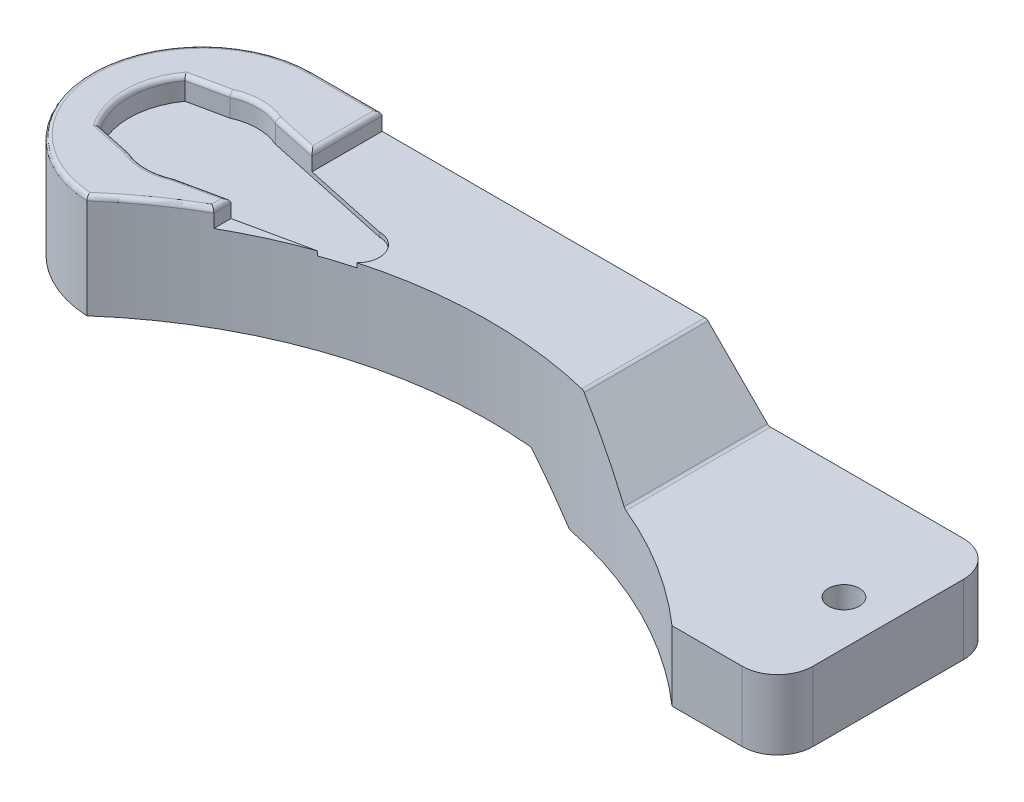
SolidWorks part; units mm, degrees
ref_plane "Front Plane" through (0, 0, 0) normal (0, 0, 1) x (1, 0, 0)
ref_plane "Top Plane" through (0, 0, 0) normal (0, 1, 0) x (1, 0, 0)
ref_plane "Right Plane" through (0, 0, 0) normal (1, 0, 0) x (0, 0, -1)
sketch "Sketch1" plane through (0, 0, 0) normal (0, 1, 0) x (1, 0, 0)
  line L1 (-45, 12.5) -> (45, 12.5)
  line L2 (-45, 12.5) -> (-45, -12.5)
  line L3 (-45, -12.5) -> (45, -12.5)
  line L4 (45, 12.5) -> (45, -12.5)
  dimension "D1" = 90
  dimension "D2" = 45
  dimension "D3" = 25
  dimension "D4" = 12.5
extrude "Boss-Extrude1" add sketch "Sketch1" along normal blind 16.87
sketch "Sketch3" plane through (0, 16.87, 0) normal (0, 1, 0) x (1, 0, 0)
  line L0 (-39.2721, 4.7988) -> (-35.061, 5.7012)
  line L5 (-45, 12.5) -> (-45, -12.5) construction
  line L6 (-45, -12.5) -> (45, -12.5) construction
  line L7 (-39.2721, -4.7988) -> (-35.061, -5.7012)
  line L9 (-29.939, 5.7012) -> (-15, 2.5)
  line L11 (-29.939, -5.7012) -> (-15, -2.5)
  arc A0 (-29.939, 5.7012) -> (-35.061, 5.7012) centre (-32.5, 0) ccw
  arc A1 (-15, -2.5) -> (-15, 2.5) centre (-15, 0) ccw
  arc A3 (-35.061, -5.7012) -> (-29.939, -5.7012) centre (-32.5, 0) ccw
  arc A4 (-39.2721, -4.7988) -> (-39.2721, 4.7988) centre (-32.5, 0) cw
  point P4 (0, 0)
  point P5 (-40.8, 0)
  point P10 (0, 0)
  point P12 (0, 0)
  dimension "D1" = 12.5
  dimension "D2" = 5
  dimension "D3" = 4.3067
  dimension "D14" = 8.3
  dimension "D4" = 4.3067
  dimension "D5" = 17.5
  dimension "D6" = 12.5
  dimension "D7" = 12.5
  dimension "D8" = 12.5
  dimension "D9" = 6.7721
  dimension "D10" = 6.7721
  dimension "D11" = 14.939
  dimension "D12" = 14.939
extrude "Cut-Extrude2" cut sketch "Sketch3" against normal blind 2.5
sketch "Esquisse2" plane through (0, 0, 12.5) normal (0, 0, 1) x (1, 0, 0)
  line L0 (10, 16.87) -> (19, 7.87)
  line L1 (45, 16.87) -> (10, 16.87)
  line L2 (45, 16.87) -> (45, 7.87)
  line L3 (45, 7.87) -> (10, 7.87)
  line L4 (10, 16.87) -> (10, 7.87)
  line L5 (-45, 0) -> (10, 0)
  line L8 (10, 0) -> (10, 7.87)
  line L9 (10, 0) -> (4.88, 5.12)
  line L10 (4.88, 5.12) -> (-45, 5.12)
  line L11 (-45, 5.12) -> (-45, 0)
  line M3 (-45, 0) -> (45, 0)
  line M4 (45, 0) -> (45, 16.87)
  line M5 (45, 16.87) -> (-45, 16.87)
  line M6 (-45, 16.87) -> (-45, 0)
  dimension "D1" = 35
  dimension "D2" = 9
  dimension "D3" = 45
  dimension "D4" = 45
  dimension "D5" = 2.75
extrude "Enlèv. mat.-Extru.1" cut sketch "Esquisse2" against normal blind 34 contours L8 M3 M6 | L4 L3 M5 M4 region at (29.6393, 12.5913, 12.5) region at (-18.7592, 2.5183, 12.5)
fillet "Fillet1" 2 edges at (-45, 10.995, 12.5) (-45, 10.995, -12.5) type full round first side face at (5.485, 7.465, 12.5) second side face at (5.485, 7.465, -12.5) middle face at (-45, 10.995, 0)
sketch "Esquisse5" plane through (0, 0, 0) normal (0, -1, 0) x (-1, 0, 0)
  line L0 (-45, -12.5) -> (-45, 12.5) construction
  circle A0 centre (-40, 0) radius 1.75
  dimension "D2" = 3.5
  dimension "D1" = 5
extrude "Enlèv. mat.-Extru.4" cut sketch "Esquisse5" against normal through all
fillet "Fillet3" radius 4 2 edges at (45, 3.935, -12.5) (45, 3.935, 12.5)
sketch "Sketch8" plane through (0, 16.87, 0) normal (0, 1, 0) x (1, 0, 0)
  line L1 (-24.6881, 14.1476) -> (13.3414, 14.1476)
  line L2 (-24.6881, 14.1476) -> (-24.6881, -6.796)
  line L3 (-24.6881, -6.796) -> (13.3414, -6.796)
  line L4 (13.3414, 14.1476) -> (13.3414, -6.796)
  dimension "D1" = 38.0295
  dimension "D2" = 20.9436
  dimension "D3" = 14.1476
  dimension "D4" = 24.6881
extrude "Cut-Extrude6" cut sketch "Sketch8" against normal blind 2
sketch "Esquisse17" plane through (0, 5.12, 0) normal (0, -1, 0) x (1, 0, 0)
  circle A0 centre (-32.5, 0) radius 6.45
  dimension "D1" = 12.9
extrude "Enlèv. mat.-Extru.7" cut sketch "Esquisse17" against normal blind 3.6
sketch "Esquisse18" plane through (0, 0, 0) normal (0, 1, 0) x (1, 0, 0)
  circle A0 centre (0, -50) radius 50
  dimension "D2" = 100
  dimension "D1" = 50
extrude "Enlèv. mat.-Extru.8" cut sketch "Esquisse18" against normal through all and the other way through all
fillet "Fillet4" radius 0.5 14 edges at (-28.5941, 16.87, -12.5) (19, 7.87, -4.3747) (12, 14.87, -5.5193) (-37.1665, 16.87, -5.25) (-27.3136, 16.87, -5.1386) (-32.5, 16.87, -6.25) (-37.1665, 16.87, 5.25) (-24.6881, 16.87, 5.5481) (-27.3136, 16.87, 5.1386) (-32.5, 16.87, 6.25) (-40.8, 16.87, 0) (-24.6881, 16.87, -8.538) (-29.0267, 16.87, 9.2882) (-44.9969, 16.87, -0.279)
